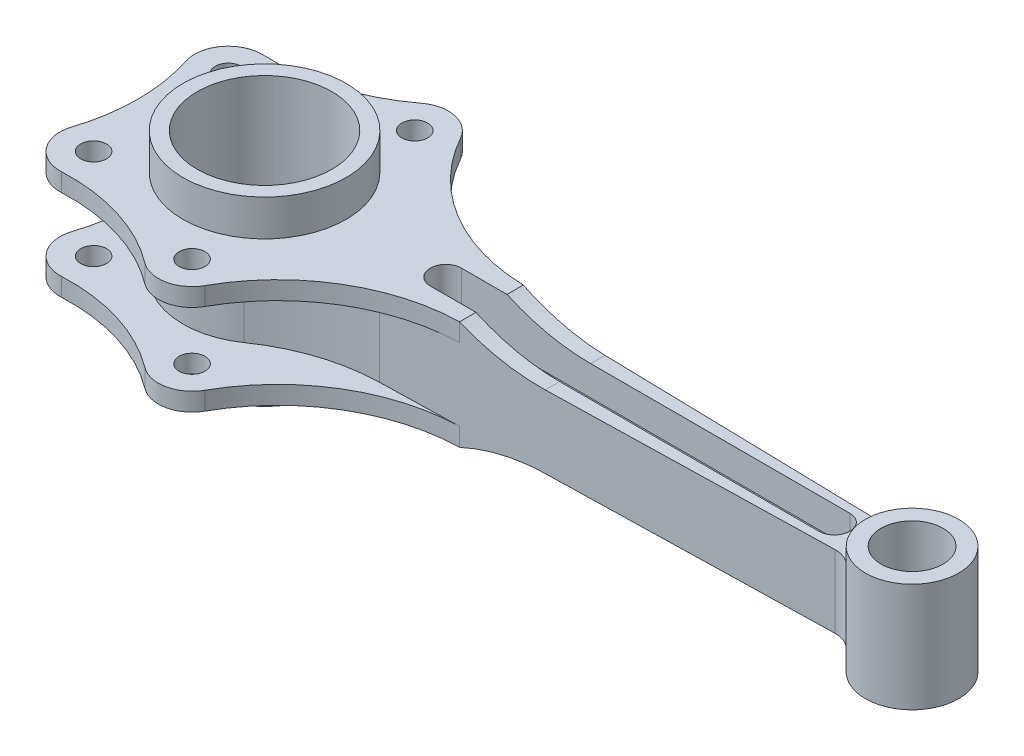
SolidWorks part; units mm, degrees
ref_plane "Front Plane" through (0, 0, 0) normal (0, 0, 1) x (1, 0, 0)
ref_plane "Top Plane" through (0, 0, 0) normal (0, 1, 0) x (1, 0, 0)
ref_plane "Right Plane" through (0, 0, 0) normal (1, 0, 0) x (0, 0, -1)
sketch "Sketch1" plane through (0, 0, 0) normal (0, 1, 0) x (1, 0, 0)
  line L0 (-185.3529, 0) -> (323.11, 0) construction
  line L1 (0, 65.6856) -> (0, -65.6856) construction
  line L2 (250, 65.6856) -> (250, -65.6856) construction
  line L3 (57.405, -13) -> (229.1978, -9)
  line L6 (57.405, 13) -> (229.1978, 9)
  line L7 (57.405, 13) -> (28.6923, 13) construction
  line L8 (57.405, -13) -> (28.6923, -13) construction
  line L9 (87, 28.8054) -> (87, -35.356) construction
  line L10 (87, 12.3109) -> (87, -12.3109)
  circle A0 centre (0, 0) radius 26
  circle A1 centre (0, 0) radius 31.5
  circle A2 centre (250, 0) radius 18
  circle A3 centre (250, 0) radius 12
  arc A6 (17.9812, 25.8636) -> (57.405, 13) centre (59.081, 84.9805) ccw
  arc A7 (229.1978, 9) -> (236.7768, 12.2125) centre (229.4305, 18.9973) ccw
  arc A8 (229.1978, -9) -> (236.7768, -12.2125) centre (229.4305, -18.9973) cw
  arc A9 (17.9812, -25.8636) -> (57.405, -13) centre (59.081, -84.9805) cw
  point P7 (0, 0)
  dimension "D2" = 24
  dimension "D3" = 52
  dimension "D4" = 9
  dimension "D6" = 10
  dimension "D8" = 72
  dimension "D9" = 36
  dimension "D10" = 63
  dimension "D1" = 250
  dimension "D5" = 13
  dimension "D7" = 87
extrude "Boss-Extrude1" add sketch "Sketch1" along normal mid plane 70 contours A1 A0 region at (-30.609, 0, 0)
extrude "Boss-Extrude2" add sketch "Sketch1<3>" along normal mid plane 42 separate body contours A2 A3 region at (232.5091, 0, 0)
sketch "Sketch1<3>" plane through (0, 0, 0) normal (0, 1, 0) x (1, 0, 0) same geometry as "Sketch1"
extrude "Boss-Extrude3" add sketch "Sketch1<5>" along normal mid plane 35 contours A1 A9 L3 L10 L6 A6 region at (55.8572, 0, 0)
sketch "Sketch1<5>" plane through (0, 0, 0) normal (0, 1, 0) x (1, 0, 0) same geometry as "Sketch1"
extrude "Boss-Extrude4" add sketch "Sketch1<6>" along normal mid plane 28 contours L3 A8 A2 A7 L6 L10 region at (156.1732, 0, 0)
sketch "Sketch1<6>" plane through (0, 0, 0) normal (0, 1, 0) x (1, 0, 0) same geometry as "Sketch1"
ref_plane "Plane1" through (0, 14, 0) normal (0, 1, 0) x (1, 0, 0)
sketch "Sketch3" plane through (0, 14, 0) normal (0, 1, 0) x (1, 0, 0)
  line L0 (0, 74.8247) -> (0, -78.1832) construction
  line L1 (-80.5102, 0) -> (153.8608, 0) construction
  line L2 (15, 63.3338) -> (15, 22.6662) construction
  line L3 (30.9992, 43) -> (-0.9992, 43) construction
  line L4 (-69.2098, 26) -> (-10.7902, 26) construction
  line L5 (-40, 45.0977) -> (-40, 6.9023) construction
  line L6 (57.405, 13) -> (87, 12.3109) construction
  line L7 (87.629, 12.2963) -> (87.629, -12.2963)
  circle A0 centre (15, 43) radius 5
  circle A1 centre (-40, 26) radius 5
  arc A2 (26.3643, 49.3129) -> (7.1819, 53.3864) centre (15, 43) ccw
  arc A3 (-39.4063, 38.9864) -> (-52.3769, 22.0235) centre (-40, 26) ccw
  arc A4 (26.3643, 49.3129) -> (87.629, 12.2963) centre (89.305, 84.2768) ccw
  arc A5 (-39.4063, 38.9864) -> (7.1819, 53.3864) centre (-36.118, 110.9113) ccw
  circle A6 centre (-40, -26) radius 5
  circle A7 centre (15, -43) radius 5
  arc A8 (26.3643, -49.3129) -> (87.629, -12.2963) centre (89.305, -84.2768) cw
  arc A9 (26.3643, -49.3129) -> (7.1819, -53.3864) centre (15, -43) cw
  arc A10 (-39.4063, -38.9864) -> (7.1819, -53.3864) centre (-36.118, -110.9113) cw
  arc A11 (-39.4063, -38.9864) -> (-52.3769, -22.0235) centre (-40, -26) cw
  arc A12 (-52.3769, -22.0235) -> (-52.3769, 22.0235) centre (-120.9259, 0) ccw
  point P13 (15, 43)
  point P14 (15, 43)
  point P15 (-40, 26)
  point P16 (-40, 26)
  dimension "D5" = 10
  dimension "D6" = 26
  dimension "D7" = 72
  dimension "D1" = 15
  dimension "D2" = 43
  dimension "D3" = 26
  dimension "D4" = 40
extrude "Boss-Extrude5" add sketch "Sketch3" along normal blind 7
mirror "Mirror1" about plane through (0, 0, 0) normal (0, 1, 0) of "Boss-Extrude5"
sketch "Sketch4" plane through (0, 0, 0) normal (0, 0, 1) x (1, 0, 0)
  line L0 (97.4989, 14) -> (-97.4989, 14) construction
  line L4 (87.629, 14) -> (229.1978, 14) construction
  line L5 (87.629, 21) -> (87.629, 14)
  line L6 (87.629, 14) -> (119.9245, 14)
  line L7 (61.6, 0) -> (-61.6, 0) construction
  line L8 (87.629, -21) -> (87.629, -14)
  line L9 (87.629, -14) -> (119.9245, -14)
  arc A0 (87.629, 21) -> (119.9245, 14) centre (119.9245, 92) ccw
  arc A1 (87.629, -21) -> (119.9245, -14) centre (119.9245, -92) cw
  dimension "D1" = 78
extrude "Boss-Extrude6" add sketch "Sketch4" along normal up to surface (12.2963 mm away) up to face at (124.7439, 0, 11.4321)
sketch "Sketch5" plane through (0, 0, 0) normal (0, 0, -1) x (-1, 0, 0)
  line L0 (61.6, 0) -> (-61.6, 0) construction
  line L1 (-119.9245, -14) -> (-87.629, -14)
  line L2 (-119.9245, 14) -> (-87.629, 14)
  line L3 (-87.629, 14) -> (-87.629, 21)
  line L4 (-119.9245, 14) -> (-87.629, 14)
  line L5 (-87.629, 14) -> (-87.629, 21)
  line L6 (-87.629, -14) -> (-87.629, -21)
  arc A0 (-119.9245, -14) -> (-87.629, -21) centre (-119.9245, -92) cw
  arc A1 (-119.9245, 14) -> (-87.629, 21) centre (-119.9245, 92) ccw
  arc A2 (-119.9245, 14) -> (-87.629, 21) centre (-119.9245, 92) ccw
  dimension "D1" = 0
extrude "Boss-Extrude9" add sketch "Sketch5" along normal up to surface (11.5443 mm away) up to face at (124.7439, 0, -11.4321)
sketch "Sketch6" plane through (0, 21, 0) normal (0, 1, 0) x (1, 0, 0)
  circle A1 centre (0, 0) radius 26
  circle A2 centre (0, 0) radius 26
  dimension "D1" = 0
extrude "Cut-Extrude1" cut sketch "Sketch6" against normal up to surface (42 mm away) up to face at (0, -21, -26)
ref_plane "Plane2" through (0, 2.5, 0) normal (0, 1, 0) x (1, 0, 0)
sketch "Sketch7" plane through (0, 2.5, 0) normal (0, 1, 0) x (1, 0, 0)
  line L0 (-112.5786, 0) -> (332.3205, 0) construction
  line L1 (250, 83.9961) -> (250, -78.4408) construction
  line L2 (238, 79.3308) -> (238, -78.4408) construction
  line L3 (0, 94.9924) -> (0, -88.6434) construction
  line L4 (220, 78.8858) -> (220, -78.8858) construction
  line L5 (220, 0) -> (70, 0) construction
  line L6 (220, -6) -> (70, -6)
  line L7 (220, 6) -> (70, 6)
  arc A0 (220, -6) -> (220, 6) centre (220, 0) ccw
  arc A1 (70, 6) -> (70, -6) centre (70, 0) ccw
  circle A2 centre (250, 0) radius 12 construction
  point P13 (220, 0)
  point P16 (145, 0)
  dimension "D4" = 6
  dimension "D1" = 12
  dimension "D2" = 30
  dimension "D3" = 150
extrude "Cut-Extrude2" cut sketch "Sketch7" along normal blind 23
mirror "Mirror2" about plane through (0, 0, 0) normal (0, 1, 0) of "Cut-Extrude2"
